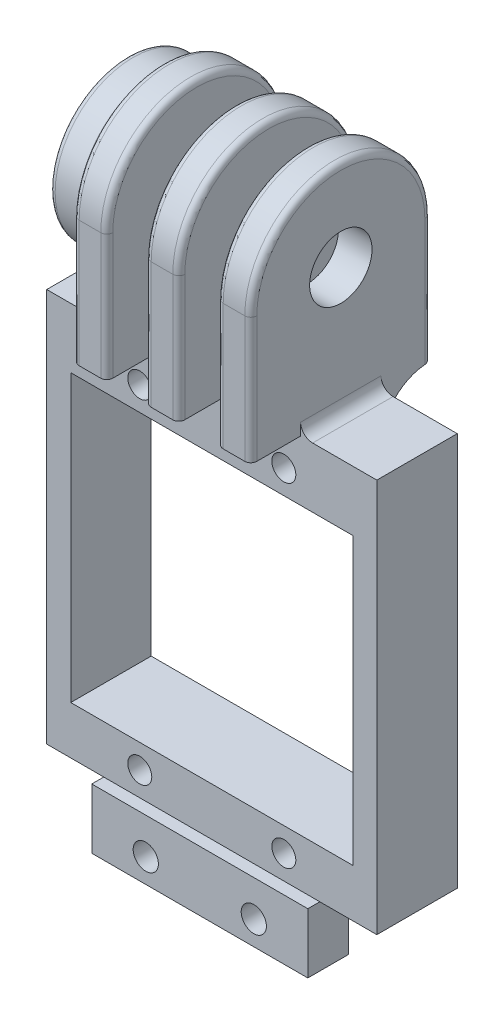
SolidWorks part; units mm, degrees
ref_plane "Front Plane" through (0, 0, 0) normal (0, 0, 1) x (1, 0, 0)
ref_plane "Top Plane" through (0, 0, 0) normal (0, 1, 0) x (1, 0, 0)
ref_plane "Right Plane" through (0, 0, 0) normal (1, 0, 0) x (0, 0, -1)
sketch "Sketch1" plane through (0, 0, 0) normal (0, 0, 1) x (1, 0, 0)
  line L0 (0, 0) -> (0, 21.5273) construction
  line L2 (-9, -2.5) -> (9, -2.5)
  line L3 (-9, -2.5) -> (-9, 2.5)
  line L4 (-9, 2.5) -> (9, 2.5)
  line L5 (9, -2.5) -> (9, 2.5)
  line L6 (-9, -2.5) -> (9, 2.5) construction
  line L7 (-9, 2.5) -> (9, -2.5) construction
  dimension "D1" = 18
  dimension "D2" = 5
extrude "Boss-Extrude1" add sketch "Sketch1" along normal blind 3.4
sketch "Sketch2" plane through (0, 0, 3.4) normal (0, 0, 1) x (1, 0, 0)
  line L0 (0, 0) -> (0, 7.329) construction
  line L1 (9, 2.5) -> (-9, 2.5) construction
  line L2 (-13.75, 6.5) -> (13.75, 6.5)
  line L3 (-13.75, 6.5) -> (-13.75, 2.5)
  line L4 (-13.75, 2.5) -> (13.75, 2.5)
  line L5 (13.75, 6.5) -> (13.75, 2.5)
  line L6 (-13.75, 6.5) -> (13.75, 2.5) construction
  line L7 (-13.75, 2.5) -> (13.75, 6.5) construction
  point P3 (0, 4.5)
  dimension "D1" = 4
  dimension "D2" = 27.5
extrude "Boss-Extrude2" add sketch "Sketch2" against normal blind 8.7
sketch "Sketch3" plane through (0, 6.5, 0) normal (0, 1, 0) x (1, 0, 0)
  line L0 (-11.75, -3.4) -> (11.75, -3.4) construction
  line L1 (-13.75, 5.3) -> (-11.75, 5.3)
  line L2 (-13.75, 5.3) -> (-13.75, -3.4)
  line L3 (-13.75, -3.4) -> (-11.75, -3.4)
  line L4 (-11.75, 5.3) -> (-11.75, -3.4)
  line L5 (13.75, 5.3) -> (11.75, 5.3)
  line L6 (13.75, 5.3) -> (13.75, -3.4)
  line L7 (13.75, -3.4) -> (11.75, -3.4)
  line L8 (11.75, 5.3) -> (11.75, -3.4)
  line L9 (13.75, -3.4) -> (-13.75, -3.4) construction
  dimension "D1" = 2
  dimension "D2" = 2
extrude "Boss-Extrude3" add sketch "Sketch3" along normal blind 23.8
sketch "Sketch4" plane through (0, 30.3, 0) normal (0, 1, 0) x (1, 0, 0)
  line L1 (-13.75, 5.3) -> (13.75, 5.3)
  line L2 (-13.75, 5.3) -> (-13.75, -3.4)
  line L3 (-13.75, -3.4) -> (13.75, -3.4)
  line L4 (13.75, 5.3) -> (13.75, -3.4)
extrude "Boss-Extrude4" add sketch "Sketch4" along normal blind 5
sketch "Sketch5" plane through (0, 0, 3.4) normal (0, 0, 1) x (1, 0, 0)
  line L0 (-9, -0.5) -> (9, -0.5) construction
  line L1 (-9, 2.5) -> (-9, -2.5) construction
  line L2 (9, -2.5) -> (9, 2.5) construction
  line L3 (0, -0.5) -> (0, 11.0457) construction
  line L4 (0, 11.0457) -> (-4.5, -0.5) construction
  line L5 (0, 11.0457) -> (4.5, -0.5) construction
  line L6 (-9, -2.5) -> (9, -2.5) construction
  line L7 (-13.75, 4.5) -> (13.75, 4.5) construction
  line L8 (-13.75, 35.3) -> (-13.75, 2.5) construction
  line L9 (13.75, 2.5) -> (13.75, 35.3) construction
  line L10 (-6, 4.5) -> (0, 11.0457) construction
  line L11 (0, 11.0457) -> (6, 4.5) construction
  line L12 (11.75, 6.5) -> (-11.75, 6.5) construction
  line L13 (-13.75, 32.3) -> (13.75, 32.3) construction
  line L14 (0, 32.3) -> (0, 4.5) construction
  line L15 (0, 18.4) -> (13.75, 18.4) construction
  line L16 (-11.75, 30.3) -> (11.75, 30.3) construction
  circle A0 centre (-4.5, -0.5) radius 1.05
  circle A1 centre (4.5, -0.5) radius 1.05
  circle A2 centre (-6, 4.5) radius 1
  circle A3 centre (6, 4.5) radius 1
  circle A4 centre (6, 32.3) radius 1
  circle A5 centre (-6, 32.3) radius 1
  dimension "D1" = 2.1
  dimension "D4" = 2
  dimension "D2" = 9
  dimension "D3" = 2
  dimension "D5" = 12
  dimension "D6" = 2
  dimension "D7" = 2
extrude "Cut-Extrude1" cut sketch "Sketch5" against normal through all
ref_plane "Plane1" through (0, 2.5, 0) normal (0, -1, 0) x (-1, 0, 0)
split "Split1" trim tools "Plane1" bodies to split 105 resulting bodies 106 107
move or copy body "Body-Move/Copy1" bodies to move or copy 107 copy no translate (0, 0, -1)
sketch "Sketch6" plane through (0, 0, -6.3) normal (0, 0, -1) x (-1, 0, 0)
  line L1 (-98.1715, 88.6754) -> (39.1083, 88.6754)
  line L2 (-98.1715, 88.6754) -> (-98.1715, -3.1678)
  line L3 (-98.1715, -3.1678) -> (39.1083, -3.1678)
  line L4 (39.1083, 88.6754) -> (39.1083, -3.1678)
  line L5 (-98.1715, 88.6754) -> (39.1083, -3.1678) construction
  line L6 (-98.1715, -3.1678) -> (39.1083, 88.6754) construction
  point P0 (-29.5316, 42.7538)
extrude "Cut-Extrude2" cut sketch "Sketch6" against normal blind 2
combine bodies "Combine1" operation type add bodies to combine 106 109
sketch "Sketch7" plane through (0, 35.3, 0) normal (0, 1, 0) x (1, 0, 0)
  line L0 (-13.75, 0.95) -> (13.75, 0.95) construction
  line L1 (-13.75, 4.3) -> (-13.75, -2.4) construction
  line L2 (13.75, -2.4) -> (13.75, 4.3) construction
  line L4 (-1.4, -6.55) -> (1.4, -6.55)
  line L5 (-1.4, -6.55) -> (-1.4, 8.45)
  line L6 (-1.4, 8.45) -> (1.4, 8.45)
  line L7 (1.4, -6.55) -> (1.4, 8.45)
  line L8 (-1.4, -6.55) -> (1.4, 8.45) construction
  line L9 (-1.4, 8.45) -> (1.4, -6.55) construction
  line L10 (4.6, -6.55) -> (7.4, -6.55)
  line L11 (4.6, -6.55) -> (4.6, 8.45)
  line L12 (4.6, 8.45) -> (7.4, 8.45)
  line L13 (7.4, -6.55) -> (7.4, 8.45)
  line L14 (4.6, -6.55) -> (7.4, 8.45) construction
  line L15 (4.6, 8.45) -> (7.4, -6.55) construction
  line L16 (-7.4, -6.55) -> (-4.6, -6.55)
  line L17 (-7.4, -6.55) -> (-7.4, 8.45)
  line L18 (-7.4, 8.45) -> (-4.6, 8.45)
  line L19 (-4.6, -6.55) -> (-4.6, 8.45)
  line L20 (-7.4, -6.55) -> (-4.6, 8.45) construction
  line L21 (-7.4, 8.45) -> (-4.6, -6.55) construction
  point P6 (0, 0.95)
  point P11 (6, 0.95)
  point P16 (-6, 0.95)
  dimension "D1" = 15
  dimension "D2" = 2.8
  dimension "D3" = 3.2
  dimension "D4" = 3.2
extrude "Boss-Extrude5" add sketch "Sketch7" along normal blind 18
sketch "Sketch8" plane through (-7.4, 0, 0) normal (-1, 0, 0) x (0, 0, 1)
  line L0 (-0.95, 53.3) -> (-0.95, 31.9277) construction
  line L1 (-8.45, 53.3) -> (6.55, 53.3) construction
  line L2 (6.55, 53.3) -> (6.55, 35.3) construction
  line L3 (-8.45, 45.8) -> (-8.45, 56.1268)
  line L4 (-8.45, 56.1268) -> (6.55, 56.1268)
  line L5 (6.55, 56.1268) -> (6.55, 45.8)
  circle A0 centre (-0.95, 45.8) radius 7.5
  circle A1 centre (-0.95, 45.8) radius 2.6
  line M4 (6.55, 35.3) -> (6.55, 53.3)
  line M5 (6.55, 53.3) -> (-8.45, 53.3)
  line M6 (-8.45, 53.3) -> (-8.45, 35.3)
  dimension "D1" = 5.2
extrude "Cut-Extrude3" cut sketch "Sketch8" against normal through all contours A0 M5 M6 | A0 M4 M5 | A1 L0 | L0 A1 region at (-7.4, 51.6247, 4.8747) region at (-7.4, 51.6247, -6.7747) region at (-7.4, 45.8, 0.1535) region at (-7.4, 45.8, -2.0535)
sketch "Sketch9" plane through (-7.4, 0, 0) normal (-1, 0, 0) x (0, 0, 1)
  circle A0 centre (-0.95, 45.8) radius 2.6 construction
  circle A1 centre (-0.95, 45.8) radius 2.6
  circle A2 centre (-0.95, 45.8) radius 6.5
  dimension "D1" = 13
extrude "Boss-Extrude6" add sketch "Sketch9" along normal blind 3
sketch "Sketch10" plane through (-10.4, 0, 0) normal (-1, 0, 0) x (0, 0, 1)
  line L1 (3.15, 43.4329) -> (3.15, 48.1671)
  line L2 (3.15, 48.1671) -> (-0.95, 50.5343)
  line L3 (-0.95, 50.5343) -> (-5.05, 48.1671)
  line L4 (-5.05, 48.1671) -> (-5.05, 43.4329)
  line L5 (-5.05, 43.4329) -> (-0.95, 41.0657)
  line L6 (-0.95, 41.0657) -> (3.15, 43.4329)
  circle A0 centre (-0.95, 45.8) radius 4.1 construction
  dimension "D1" = 8.2
extrude "Cut-Extrude4" cut sketch "Sketch10" against normal blind 4
fillet "Fillet1" radius 0.5 20 edges at (-4.6, 40.55, 6.55) (-4.6, 40.55, -8.45) (-4.6, 53.3, -0.95) (-7.4, 45.8, -7.45) (-10.4, 45.8, 5.55) (7.4, 40.55, 6.55) (7.4, 40.55, -8.45) (4.6, 40.55, -8.45) (4.6, 40.55, 6.55) (1.4, 40.55, 6.55) (1.4, 40.55, -8.45) (-1.4, 40.55, -8.45) (-1.4, 40.55, 6.55) (-7.4, 40.55, 6.55) (-7.4, 40.55, -8.45) (7.4, 53.3, -0.95) (4.6, 53.3, -0.95) (1.4, 53.3, -0.95) (-1.4, 53.3, -0.95) (-7.4, 53.3, -0.95)
fillet "Fillet2" radius 4 3 edges at (6, 35.3, -4.3) (0, 35.3, -4.3) (-6, 35.3, -4.3)
fillet "Fillet3" radius 1 6 edges at (7.4, 35.3, -0.95) (4.6, 35.3, -0.95) (1.4, 35.3, -0.95) (-1.4, 35.3, -0.95) (-4.6, 35.3, -0.95) (-7.4, 35.3, -0.95)
